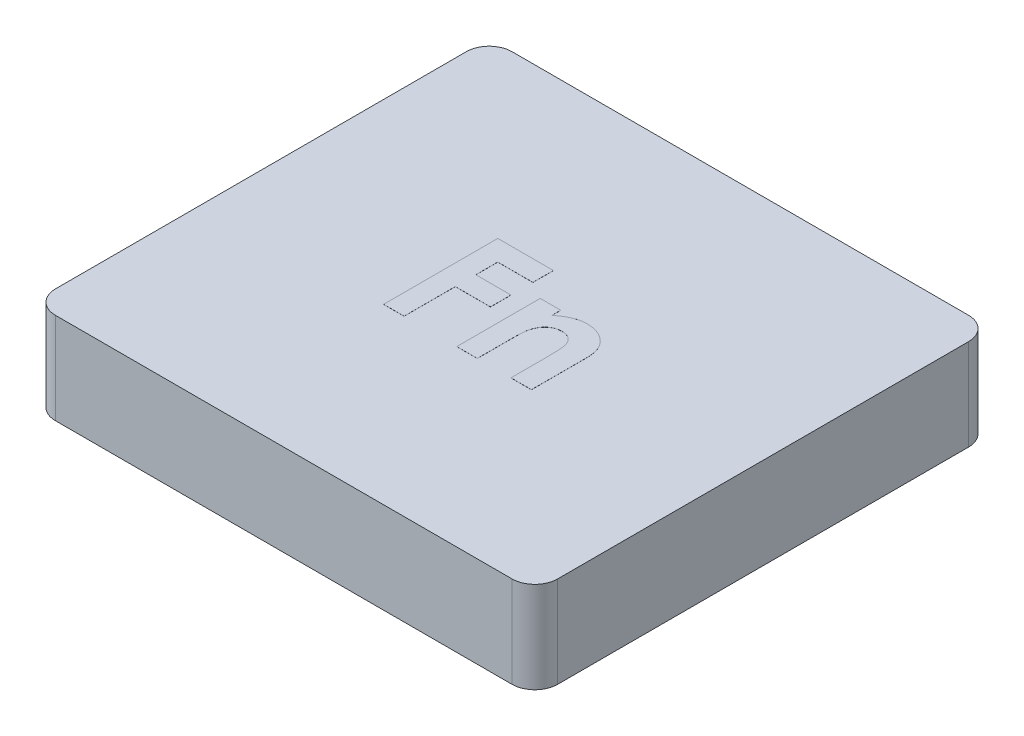
SolidWorks part; units mm, degrees
ref_plane "Front Plane" through (0, 0, 0) normal (0, 0, 1) x (1, 0, 0)
ref_plane "Top Plane" through (0, 0, 0) normal (0, 1, 0) x (1, 0, 0)
ref_plane "Right Plane" through (0, 0, 0) normal (1, 0, 0) x (0, 0, -1)
sketch "Sketch1" plane through (0, 0, 0) normal (0, 1, 0) x (1, 0, 0)
  line L0 (0, 0) -> (13.97, 0)
  line L1 (13.97, 0) -> (13.97, 12.7)
  line L2 (13.97, 12.7) -> (0, 12.7)
  line L3 (0, 12.7) -> (0, 0)
  dimension "D1" = 13.97
  dimension "D2" = 12.7
extrude "Boss-Extrude1" add sketch "Sketch1" along normal blind 2.54
fillet "Fillet1" radius 0.635 4 edges at (0, 1.27, -12.7) (13.97, 1.27, -12.7) (13.97, 1.27, 0) (0, 1.27, 0)
shell "Shell1" thickness 0.635 removed face at (6.985, 0, -6.35)
sketch "Sketch2" plane through (0, 1.905, 0) normal (0, -1, 0) x (-1, 0, 0)
  line L0 (-0.635, 6.35) -> (-13.335, 6.35) construction
  line L1 (-0.635, 12.065) -> (-0.635, 0.635) construction
  line L2 (-13.335, 0.635) -> (-13.335, 12.065) construction
  line L3 (-6.985, 0.635) -> (-6.985, 12.065) construction
  line L4 (-0.635, 0.635) -> (-13.335, 0.635) construction
  line L5 (-13.335, 12.065) -> (-0.635, 12.065) construction
  circle A0 centre (-6.985, 6.35) radius 2.54
  dimension "D1" = 5.08
extrude "Boss-Extrude2" add sketch "Sketch2" along normal up to surface (1.905 mm away) up to face at (6.985, 0, -6.35)
sketch "Sketch3" plane through (0, 2.54, 0) normal (0, 1, 0) x (1, 0, 0)
  line L0 (0, 12.065) -> (0, 0.635) construction
  line L1 (13.335, 12.7) -> (0.635, 12.7) construction
  text T0 "<b>Fn</b>"
  dimension "D1" = 4.572
  dimension "D2" = 7.874
extrude "Boss-Extrude3" add sketch "Sketch3" along normal blind 0.0025
